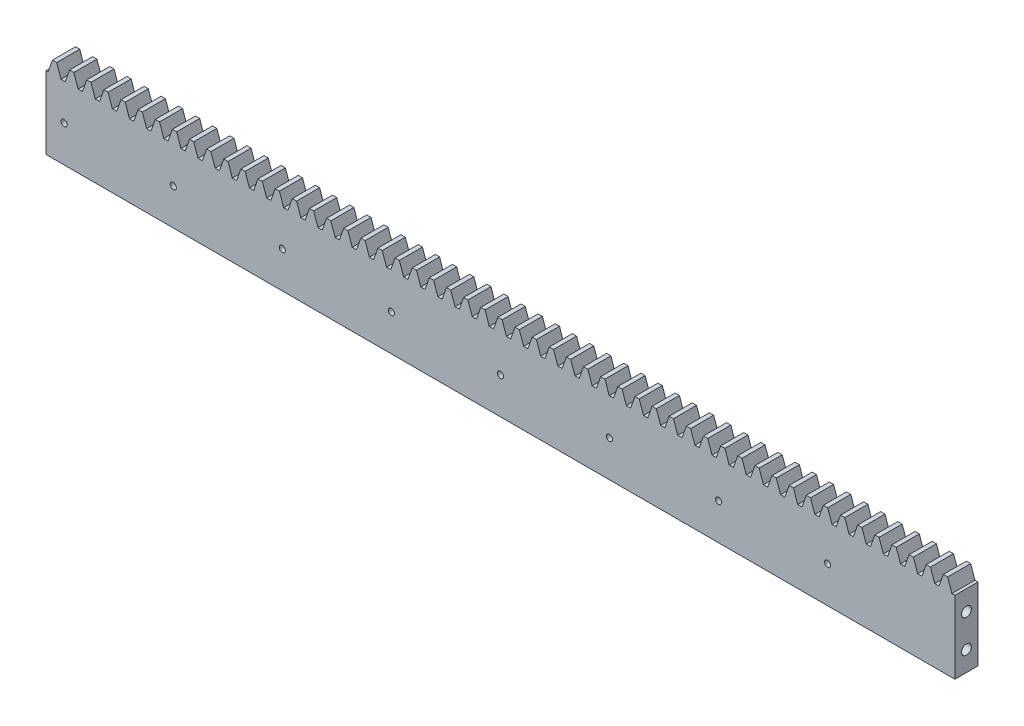
SolidWorks part; units mm, degrees
ref_plane "Front Plane" through (0, 0, 0) normal (0, 0, 1) x (1, 0, 0)
ref_plane "Top Plane" through (0, 0, 0) normal (0, 1, 0) x (1, 0, 0)
ref_plane "Right Plane" through (0, 0, 0) normal (1, 0, 0) x (0, 0, -1)
sketch "Original Sketch" plane through (0, 0, 0) normal (0, 0, 1) x (1, 0, 0)
  line L0 (5.3011, 16.625) -> (4.1236, 16.625) construction
  line L1 (4.1236, 16.625) -> (2.9446, 20) construction
  line L2 (2.9446, 20) -> (1.7677, 20) construction
  line L3 (1.7677, 20) -> (0.5887, 16.625) construction
  line L4 (0.5887, 16.625) -> (0, 16.625) construction
  line L5 (0, 16.625) -> (0, 0) construction
  line L6 (0, 0) -> (303, 0) construction
  line L7 (303, 0) -> (303, 18.9683) construction
  line L8 (303, 18.9683) -> (302.1814, 16.625) construction
  line L9 (302.1814, 16.625) -> (301.0039, 16.625) construction
  line L10 (301.0039, 16.625) -> (299.8249, 20) construction
  line L11 (299.8249, 20) -> (298.648, 20) construction
  line L12 (298.648, 20) -> (297.469, 16.625) construction
  line L13 (297.469, 16.625) -> (296.2915, 16.625) construction
  line L14 (296.2915, 16.625) -> (295.1125, 20) construction
  line L15 (295.1125, 20) -> (293.9356, 20) construction
  line L16 (293.9356, 20) -> (292.7566, 16.625) construction
  line L17 (292.7566, 16.625) -> (291.5791, 16.625) construction
  line L18 (291.5791, 16.625) -> (290.4001, 20) construction
  line L19 (290.4001, 20) -> (289.2232, 20) construction
  line L20 (289.2232, 20) -> (288.0442, 16.625) construction
  line L21 (288.0442, 16.625) -> (286.8667, 16.625) construction
  line L22 (286.8667, 16.625) -> (285.6877, 20) construction
  line L23 (285.6877, 20) -> (284.5109, 20) construction
  line L24 (284.5109, 20) -> (283.3318, 16.625) construction
  line L25 (283.3318, 16.625) -> (282.1544, 16.625) construction
  line L26 (282.1544, 16.625) -> (280.9753, 20) construction
  line L27 (280.9753, 20) -> (279.7985, 20) construction
  line L28 (279.7985, 20) -> (278.6195, 16.625) construction
  line L29 (278.6195, 16.625) -> (277.442, 16.625) construction
  line L30 (277.442, 16.625) -> (276.263, 20) construction
  line L31 (276.263, 20) -> (275.0861, 20) construction
  line L32 (275.0861, 20) -> (273.9071, 16.625) construction
  line L33 (273.9071, 16.625) -> (272.7296, 16.625) construction
  line L34 (272.7296, 16.625) -> (271.5506, 20) construction
  line L35 (271.5506, 20) -> (270.3737, 20) construction
  line L36 (270.3737, 20) -> (269.1947, 16.625) construction
  line L37 (269.1947, 16.625) -> (268.0172, 16.625) construction
  line L38 (268.0172, 16.625) -> (266.8382, 20) construction
  line L39 (266.8382, 20) -> (265.6613, 20) construction
  line L40 (265.6613, 20) -> (264.4823, 16.625) construction
  line L41 (264.4823, 16.625) -> (263.3048, 16.625) construction
  line L42 (263.3048, 16.625) -> (262.1258, 20) construction
  line L43 (262.1258, 20) -> (260.9489, 20) construction
  line L44 (260.9489, 20) -> (259.7699, 16.625) construction
  line L45 (259.7699, 16.625) -> (258.5924, 16.625) construction
  line L46 (258.5924, 16.625) -> (257.4134, 20) construction
  line L47 (257.4134, 20) -> (256.2365, 20) construction
  line L48 (256.2365, 20) -> (255.0575, 16.625) construction
  line L49 (255.0575, 16.625) -> (253.88, 16.625) construction
  line L50 (253.88, 16.625) -> (252.701, 20) construction
  line L51 (252.701, 20) -> (251.5242, 20) construction
  line L52 (251.5242, 20) -> (250.3452, 16.625) construction
  line L53 (250.3452, 16.625) -> (249.1677, 16.625) construction
  line L54 (249.1677, 16.625) -> (247.9887, 20) construction
  line L55 (247.9887, 20) -> (246.8118, 20) construction
  line L56 (246.8118, 20) -> (245.6328, 16.625) construction
  line L57 (245.6328, 16.625) -> (244.4553, 16.625) construction
  line L58 (244.4553, 16.625) -> (243.2763, 20) construction
  line L59 (243.2763, 20) -> (242.0994, 20) construction
  line L60 (242.0994, 20) -> (240.9204, 16.625) construction
  line L61 (240.9204, 16.625) -> (239.7429, 16.625) construction
  line L62 (239.7429, 16.625) -> (238.5639, 20) construction
  line L63 (238.5639, 20) -> (237.387, 20) construction
  line L64 (237.387, 20) -> (236.208, 16.625) construction
  line L65 (236.208, 16.625) -> (235.0305, 16.625) construction
  line L66 (235.0305, 16.625) -> (233.8515, 20) construction
  line L67 (233.8515, 20) -> (232.6746, 20) construction
  line L68 (232.6746, 20) -> (231.4956, 16.625) construction
  line L69 (231.4956, 16.625) -> (230.3181, 16.625) construction
  line L70 (230.3181, 16.625) -> (229.1391, 20) construction
  line L71 (229.1391, 20) -> (227.9622, 20) construction
  line L72 (227.9622, 20) -> (226.7832, 16.625) construction
  line L73 (226.7832, 16.625) -> (225.6057, 16.625) construction
  line L74 (225.6057, 16.625) -> (224.4267, 20) construction
  line L75 (224.4267, 20) -> (223.2498, 20) construction
  line L76 (223.2498, 20) -> (222.0708, 16.625) construction
  line L77 (222.0708, 16.625) -> (220.8933, 16.625) construction
  line L78 (220.8933, 16.625) -> (219.7143, 20) construction
  line L79 (219.7143, 20) -> (218.5375, 20) construction
  line L80 (218.5375, 20) -> (217.3585, 16.625) construction
  line L81 (217.3585, 16.625) -> (216.181, 16.625) construction
  line L82 (216.181, 16.625) -> (215.002, 20) construction
  line L83 (215.002, 20) -> (213.8251, 20) construction
  line L84 (213.8251, 20) -> (212.6461, 16.625) construction
  line L85 (212.6461, 16.625) -> (211.4686, 16.625) construction
  line L86 (211.4686, 16.625) -> (210.2896, 20) construction
  line L87 (210.2896, 20) -> (209.1127, 20) construction
  line L88 (209.1127, 20) -> (207.9337, 16.625) construction
  line L89 (207.9337, 16.625) -> (206.7562, 16.625) construction
  line L90 (206.7562, 16.625) -> (205.5772, 20) construction
  line L91 (205.5772, 20) -> (204.4003, 20) construction
  line L92 (204.4003, 20) -> (203.2213, 16.625) construction
  line L93 (203.2213, 16.625) -> (202.0438, 16.625) construction
  line L94 (202.0438, 16.625) -> (200.8648, 20) construction
  line L95 (200.8648, 20) -> (199.6879, 20) construction
  line L96 (199.6879, 20) -> (198.5089, 16.625) construction
  line L97 (198.5089, 16.625) -> (197.3314, 16.625) construction
  line L98 (197.3314, 16.625) -> (196.1524, 20) construction
  line L99 (196.1524, 20) -> (194.9755, 20) construction
  line L100 (194.9755, 20) -> (193.7965, 16.625) construction
  line L101 (193.7965, 16.625) -> (192.619, 16.625) construction
  line L102 (192.619, 16.625) -> (191.44, 20) construction
  line L103 (191.44, 20) -> (190.2631, 20) construction
  line L104 (190.2631, 20) -> (189.0841, 16.625) construction
  line L105 (189.0841, 16.625) -> (187.9067, 16.625) construction
  line L106 (187.9067, 16.625) -> (186.7276, 20) construction
  line L107 (186.7276, 20) -> (185.5508, 20) construction
  line L108 (185.5508, 20) -> (184.3718, 16.625) construction
  line L109 (184.3718, 16.625) -> (183.1943, 16.625) construction
  line L110 (183.1943, 16.625) -> (182.0153, 20) construction
  line L111 (182.0153, 20) -> (180.8384, 20) construction
  line L112 (180.8384, 20) -> (179.6594, 16.625) construction
  line L113 (179.6594, 16.625) -> (178.4819, 16.625) construction
  line L114 (178.4819, 16.625) -> (177.3029, 20) construction
  line L115 (177.3029, 20) -> (176.126, 20) construction
  line L116 (176.126, 20) -> (174.947, 16.625) construction
  line L117 (174.947, 16.625) -> (173.7695, 16.625) construction
  line L118 (173.7695, 16.625) -> (172.5905, 20) construction
  line L119 (172.5905, 20) -> (171.4136, 20) construction
  line L120 (171.4136, 20) -> (170.2346, 16.625) construction
  line L121 (170.2346, 16.625) -> (169.0571, 16.625) construction
  line L122 (169.0571, 16.625) -> (167.8781, 20) construction
  line L123 (167.8781, 20) -> (166.7012, 20) construction
  line L124 (166.7012, 20) -> (165.5222, 16.625) construction
  line L125 (165.5222, 16.625) -> (164.3447, 16.625) construction
  line L126 (164.3447, 16.625) -> (163.1657, 20) construction
  line L127 (163.1657, 20) -> (161.9888, 20) construction
  line L128 (161.9888, 20) -> (160.8098, 16.625) construction
  line L129 (160.8098, 16.625) -> (159.6323, 16.625) construction
  line L130 (159.6323, 16.625) -> (158.4533, 20) construction
  line L131 (158.4533, 20) -> (157.2765, 20) construction
  line L132 (157.2765, 20) -> (156.0975, 16.625) construction
  line L133 (156.0975, 16.625) -> (154.92, 16.625) construction
  line L134 (154.92, 16.625) -> (153.741, 20) construction
  line L135 (153.741, 20) -> (152.5641, 20) construction
  line L136 (152.5641, 20) -> (151.3851, 16.625) construction
  line L137 (151.3851, 16.625) -> (150.2076, 16.625) construction
  line L138 (150.2076, 16.625) -> (149.0286, 20) construction
  line L139 (149.0286, 20) -> (147.8517, 20) construction
  line L140 (147.8517, 20) -> (146.6727, 16.625) construction
  line L141 (146.6727, 16.625) -> (145.4952, 16.625) construction
  line L142 (145.4952, 16.625) -> (144.3162, 20) construction
  line L143 (144.3162, 20) -> (143.1393, 20) construction
  line L144 (143.1393, 20) -> (141.9603, 16.625) construction
  line L145 (141.9603, 16.625) -> (140.7828, 16.625) construction
  line L146 (140.7828, 16.625) -> (139.6038, 20) construction
  line L147 (139.6038, 20) -> (138.4269, 20) construction
  line L148 (138.4269, 20) -> (137.2479, 16.625) construction
  line L149 (137.2479, 16.625) -> (136.0704, 16.625) construction
  line L150 (136.0704, 16.625) -> (134.8914, 20) construction
  line L151 (134.8914, 20) -> (133.7145, 20) construction
  line L152 (133.7145, 20) -> (132.5355, 16.625) construction
  line L153 (132.5355, 16.625) -> (131.358, 16.625) construction
  line L154 (131.358, 16.625) -> (130.179, 20) construction
  line L155 (130.179, 20) -> (129.0021, 20) construction
  line L156 (129.0021, 20) -> (127.8231, 16.625) construction
  line L157 (127.8231, 16.625) -> (126.6456, 16.625) construction
  line L158 (126.6456, 16.625) -> (125.4666, 20) construction
  line L159 (125.4666, 20) -> (124.2898, 20) construction
  line L160 (124.2898, 20) -> (123.1108, 16.625) construction
  line L161 (123.1108, 16.625) -> (121.9333, 16.625) construction
  line L162 (121.9333, 16.625) -> (120.7543, 20) construction
  line L163 (120.7543, 20) -> (119.5774, 20) construction
  line L164 (119.5774, 20) -> (118.3984, 16.625) construction
  line L165 (118.3984, 16.625) -> (117.2209, 16.625) construction
  line L166 (117.2209, 16.625) -> (116.0419, 20) construction
  line L167 (116.0419, 20) -> (114.865, 20) construction
  line L168 (114.865, 20) -> (113.686, 16.625) construction
  line L169 (113.686, 16.625) -> (112.5085, 16.625) construction
  line L170 (112.5085, 16.625) -> (111.3295, 20) construction
  line L171 (111.3295, 20) -> (110.1526, 20) construction
  line L172 (110.1526, 20) -> (108.9736, 16.625) construction
  line L173 (108.9736, 16.625) -> (107.7961, 16.625) construction
  line L174 (107.7961, 16.625) -> (106.6171, 20) construction
  line L175 (106.6171, 20) -> (105.4402, 20) construction
  line L176 (105.4402, 20) -> (104.2612, 16.625) construction
  line L177 (104.2612, 16.625) -> (103.0837, 16.625) construction
  line L178 (103.0837, 16.625) -> (101.9047, 20) construction
  line L179 (101.9047, 20) -> (100.7278, 20) construction
  line L180 (100.7278, 20) -> (99.5488, 16.625) construction
  line L181 (99.5488, 16.625) -> (98.3713, 16.625) construction
  line L182 (98.3713, 16.625) -> (97.1923, 20) construction
  line L183 (97.1923, 20) -> (96.0155, 20) construction
  line L184 (96.0155, 20) -> (94.8364, 16.625) construction
  line L185 (94.8364, 16.625) -> (93.659, 16.625) construction
  line L186 (93.659, 16.625) -> (92.48, 20) construction
  line L187 (92.48, 20) -> (91.3031, 20) construction
  line L188 (91.3031, 20) -> (90.1241, 16.625) construction
  line L189 (90.1241, 16.625) -> (88.9466, 16.625) construction
  line L190 (88.9466, 16.625) -> (87.7676, 20) construction
  line L191 (87.7676, 20) -> (86.5907, 20) construction
  line L192 (86.5907, 20) -> (85.4117, 16.625) construction
  line L193 (85.4117, 16.625) -> (84.2342, 16.625) construction
  line L194 (84.2342, 16.625) -> (83.0552, 20) construction
  line L195 (83.0552, 20) -> (81.8783, 20) construction
  line L196 (81.8783, 20) -> (80.6993, 16.625) construction
  line L197 (80.6993, 16.625) -> (79.5218, 16.625) construction
  line L198 (79.5218, 16.625) -> (78.3428, 20) construction
  line L199 (78.3428, 20) -> (77.1659, 20) construction
  line L200 (77.1659, 20) -> (75.9869, 16.625) construction
  line L201 (75.9869, 16.625) -> (74.8094, 16.625) construction
  line L202 (74.8094, 16.625) -> (73.6304, 20) construction
  line L203 (73.6304, 20) -> (72.4535, 20) construction
  line L204 (72.4535, 20) -> (71.2745, 16.625) construction
  line L205 (71.2745, 16.625) -> (70.097, 16.625) construction
  line L206 (70.097, 16.625) -> (68.918, 20) construction
  line L207 (68.918, 20) -> (67.7411, 20) construction
  line L208 (67.7411, 20) -> (66.5621, 16.625) construction
  line L209 (66.5621, 16.625) -> (65.3846, 16.625) construction
  line L210 (65.3846, 16.625) -> (64.2056, 20) construction
  line L211 (64.2056, 20) -> (63.0288, 20) construction
  line L212 (63.0288, 20) -> (61.8498, 16.625) construction
  line L213 (61.8498, 16.625) -> (60.6723, 16.625) construction
  line L214 (60.6723, 16.625) -> (59.4933, 20) construction
  line L215 (59.4933, 20) -> (58.3164, 20) construction
  line L216 (58.3164, 20) -> (57.1374, 16.625) construction
  line L217 (57.1374, 16.625) -> (55.9599, 16.625) construction
  line L218 (55.9599, 16.625) -> (54.7809, 20) construction
  line L219 (54.7809, 20) -> (53.604, 20) construction
  line L220 (53.604, 20) -> (52.425, 16.625) construction
  line L221 (52.425, 16.625) -> (51.2475, 16.625) construction
  line L222 (51.2475, 16.625) -> (50.0685, 20) construction
  line L223 (50.0685, 20) -> (48.8916, 20) construction
  line L224 (48.8916, 20) -> (47.7126, 16.625) construction
  line L225 (47.7126, 16.625) -> (46.5351, 16.625) construction
  line L226 (46.5351, 16.625) -> (45.3561, 20) construction
  line L227 (45.3561, 20) -> (44.1792, 20) construction
  line L228 (44.1792, 20) -> (43.0002, 16.625) construction
  line L229 (43.0002, 16.625) -> (41.8227, 16.625) construction
  line L230 (41.8227, 16.625) -> (40.6437, 20) construction
  line L231 (40.6437, 20) -> (39.4668, 20) construction
  line L232 (39.4668, 20) -> (38.2878, 16.625) construction
  line L233 (38.2878, 16.625) -> (37.1103, 16.625) construction
  line L234 (37.1103, 16.625) -> (35.9313, 20) construction
  line L235 (35.9313, 20) -> (34.7544, 20) construction
  line L236 (34.7544, 20) -> (33.5754, 16.625) construction
  line L237 (33.5754, 16.625) -> (32.3979, 16.625) construction
  line L238 (32.3979, 16.625) -> (31.2189, 20) construction
  line L239 (31.2189, 20) -> (30.0421, 20) construction
  line L240 (30.0421, 20) -> (28.8631, 16.625) construction
  line L241 (28.8631, 16.625) -> (27.6856, 16.625) construction
  line L242 (27.6856, 16.625) -> (26.5066, 20) construction
  line L243 (26.5066, 20) -> (25.3297, 20) construction
  line L244 (25.3297, 20) -> (24.1507, 16.625) construction
  line L245 (24.1507, 16.625) -> (22.9732, 16.625) construction
  line L246 (22.9732, 16.625) -> (21.7942, 20) construction
  line L247 (21.7942, 20) -> (20.6173, 20) construction
  line L248 (20.6173, 20) -> (19.4383, 16.625) construction
  line L249 (19.4383, 16.625) -> (18.2608, 16.625) construction
  line L250 (18.2608, 16.625) -> (17.0818, 20) construction
  line L251 (17.0818, 20) -> (15.9049, 20) construction
  line L252 (15.9049, 20) -> (14.7259, 16.625) construction
  line L253 (14.7259, 16.625) -> (13.5484, 16.625) construction
  line L254 (13.5484, 16.625) -> (12.3694, 20) construction
  line L255 (12.3694, 20) -> (11.1925, 20) construction
  line L256 (11.1925, 20) -> (10.0135, 16.625) construction
  line L257 (10.0135, 16.625) -> (8.836, 16.625) construction
  line L258 (8.836, 16.625) -> (7.657, 20) construction
  line L259 (7.657, 20) -> (6.4801, 20) construction
  line L260 (6.4801, 20) -> (5.3011, 16.625) construction
sketch "Sketch6" plane through (0, 0, 0) normal (0, 0, 1) x (1, 0, 0)
  line L2 (303, 0) -> (303, 18.9683) construction
  line L3 (303, 18.9683) -> (302.1814, 16.625) construction
  line L4 (302.1814, 16.625) -> (301.0039, 16.625) construction
  line L5 (301.0039, 16.625) -> (299.8249, 20) construction
  line L6 (299.8249, 20) -> (298.648, 20) construction
  line L7 (298.648, 20) -> (297.469, 16.625) construction
  line L8 (297.469, 16.625) -> (296.2915, 16.625) construction
  line L9 (296.2915, 16.625) -> (295.1125, 20) construction
  line L10 (295.1125, 20) -> (293.9356, 20) construction
  line L11 (293.9356, 20) -> (292.7566, 16.625) construction
  line L12 (292.7566, 16.625) -> (291.5791, 16.625) construction
  line L13 (291.5791, 16.625) -> (290.4001, 20) construction
  line L14 (290.4001, 20) -> (289.2232, 20) construction
  line L15 (289.2232, 20) -> (288.0442, 16.625) construction
  line L16 (288.0442, 16.625) -> (286.8667, 16.625) construction
  line L17 (286.8667, 16.625) -> (285.6877, 20) construction
  line L18 (285.6877, 20) -> (284.5109, 20) construction
  line L19 (284.5109, 20) -> (283.3318, 16.625) construction
  line L20 (283.3318, 16.625) -> (282.1544, 16.625) construction
  line L21 (282.1544, 16.625) -> (280.9753, 20) construction
  line L22 (280.9753, 20) -> (279.7985, 20) construction
  line L23 (279.7985, 20) -> (278.6195, 16.625) construction
  line L24 (278.6195, 16.625) -> (277.442, 16.625) construction
  line L25 (277.442, 16.625) -> (276.263, 20) construction
  line L26 (276.263, 20) -> (275.0861, 20) construction
  line L27 (275.0861, 20) -> (273.9071, 16.625) construction
  line L28 (273.9071, 16.625) -> (272.7296, 16.625) construction
  line L29 (272.7296, 16.625) -> (271.5506, 20) construction
  line L30 (271.5506, 20) -> (270.3737, 20) construction
  line L31 (270.3737, 20) -> (269.1947, 16.625) construction
  line L32 (269.1947, 16.625) -> (268.0172, 16.625) construction
  line L33 (268.0172, 16.625) -> (266.8382, 20) construction
  line L34 (266.8382, 20) -> (265.6613, 20) construction
  line L35 (265.6613, 20) -> (264.4823, 16.625) construction
  line L36 (264.4823, 16.625) -> (263.3048, 16.625) construction
  line L37 (263.3048, 16.625) -> (262.1258, 20) construction
  line L38 (262.1258, 20) -> (260.9489, 20) construction
  line L39 (260.9489, 20) -> (259.7699, 16.625) construction
  line L40 (259.7699, 16.625) -> (258.5924, 16.625) construction
  line L41 (258.5924, 16.625) -> (257.4134, 20) construction
  line L42 (257.4134, 20) -> (256.2365, 20) construction
  line L43 (256.2365, 20) -> (255.0575, 16.625) construction
  line L44 (255.0575, 16.625) -> (253.88, 16.625) construction
  line L45 (253.88, 16.625) -> (252.701, 20) construction
  line L46 (252.701, 20) -> (251.5242, 20) construction
  line L47 (251.5242, 20) -> (250.3452, 16.625) construction
  line L48 (250.3452, 16.625) -> (249.1677, 16.625) construction
  line L49 (249.1677, 16.625) -> (247.9887, 20) construction
  line L50 (247.9887, 20) -> (246.8118, 20) construction
  line L51 (246.8118, 20) -> (245.6328, 16.625) construction
  line L52 (245.6328, 16.625) -> (244.4553, 16.625) construction
  line L53 (244.4553, 16.625) -> (243.2763, 20) construction
  line L54 (243.2763, 20) -> (242.0994, 20) construction
  line L55 (242.0994, 20) -> (240.9204, 16.625) construction
  line L56 (240.9204, 16.625) -> (239.7429, 16.625) construction
  line L57 (239.7429, 16.625) -> (238.5639, 20) construction
  line L58 (238.5639, 20) -> (237.387, 20) construction
  line L59 (237.387, 20) -> (236.208, 16.625) construction
  line L60 (236.208, 16.625) -> (235.0305, 16.625) construction
  line L61 (235.0305, 16.625) -> (233.8515, 20) construction
  line L62 (233.8515, 20) -> (232.6746, 20) construction
  line L63 (232.6746, 20) -> (231.4956, 16.625) construction
  line L64 (231.4956, 16.625) -> (230.3181, 16.625) construction
  line L65 (230.3181, 16.625) -> (229.1391, 20) construction
  line L66 (229.1391, 20) -> (227.9622, 20) construction
  line L67 (227.9622, 20) -> (226.7832, 16.625) construction
  line L68 (226.7832, 16.625) -> (225.6057, 16.625) construction
  line L69 (225.6057, 16.625) -> (224.4267, 20) construction
  line L70 (224.4267, 20) -> (223.2498, 20) construction
  line L71 (223.2498, 20) -> (222.0708, 16.625) construction
  line L72 (222.0708, 16.625) -> (220.8933, 16.625) construction
  line L73 (220.8933, 16.625) -> (219.7143, 20) construction
  line L74 (219.7143, 20) -> (218.5375, 20) construction
  line L75 (218.5375, 20) -> (217.3585, 16.625) construction
  line L76 (217.3585, 16.625) -> (216.181, 16.625) construction
  line L77 (216.181, 16.625) -> (215.002, 20) construction
  line L78 (215.002, 20) -> (213.8251, 20) construction
  line L79 (213.8251, 20) -> (212.6461, 16.625) construction
  line L80 (212.6461, 16.625) -> (211.4686, 16.625) construction
  line L81 (211.4686, 16.625) -> (210.2896, 20) construction
  line L82 (210.2896, 20) -> (209.1127, 20) construction
  line L83 (209.1127, 20) -> (207.9337, 16.625) construction
  line L84 (207.9337, 16.625) -> (206.7562, 16.625) construction
  line L85 (206.7562, 16.625) -> (205.5772, 20) construction
  line L86 (205.5772, 20) -> (204.4003, 20) construction
  line L87 (204.4003, 20) -> (203.2213, 16.625) construction
  line L88 (203.2213, 16.625) -> (202.0438, 16.625) construction
  line L89 (202.0438, 16.625) -> (200.8648, 20) construction
  line L90 (200.8648, 20) -> (199.6879, 20) construction
  line L91 (199.6879, 20) -> (198.5089, 16.625) construction
  line L92 (198.5089, 16.625) -> (197.3314, 16.625) construction
  line L93 (197.3314, 16.625) -> (196.1524, 20) construction
  line L94 (196.1524, 20) -> (194.9755, 20) construction
  line L95 (194.9755, 20) -> (193.7965, 16.625) construction
  line L96 (193.7965, 16.625) -> (192.619, 16.625) construction
  line L97 (192.619, 16.625) -> (191.44, 20) construction
  line L98 (191.44, 20) -> (190.2631, 20) construction
  line L99 (190.2631, 20) -> (189.0841, 16.625) construction
  line L100 (189.0841, 16.625) -> (187.9067, 16.625) construction
  line L101 (187.9067, 16.625) -> (186.7276, 20) construction
  line L102 (186.7276, 20) -> (185.5508, 20) construction
  line L103 (185.5508, 20) -> (184.3718, 16.625) construction
  line L104 (184.3718, 16.625) -> (183.1943, 16.625) construction
  line L105 (183.1943, 16.625) -> (182.0153, 20) construction
  line L106 (182.0153, 20) -> (180.8384, 20) construction
  line L107 (180.8384, 20) -> (179.6594, 16.625) construction
  line L108 (179.6594, 16.625) -> (178.4819, 16.625) construction
  line L109 (178.4819, 16.625) -> (177.3029, 20) construction
  line L110 (177.3029, 20) -> (176.126, 20) construction
  line L111 (176.126, 20) -> (174.947, 16.625) construction
  line L112 (174.947, 16.625) -> (173.7695, 16.625) construction
  line L113 (173.7695, 16.625) -> (172.5905, 20) construction
  line L114 (172.5905, 20) -> (171.4136, 20) construction
  line L115 (171.4136, 20) -> (170.2346, 16.625) construction
  line L116 (170.2346, 16.625) -> (169.0571, 16.625) construction
  line L117 (169.0571, 16.625) -> (167.8781, 20) construction
  line L118 (167.8781, 20) -> (166.7012, 20) construction
  line L119 (166.7012, 20) -> (165.5222, 16.625) construction
  line L120 (165.5222, 16.625) -> (164.3447, 16.625) construction
  line L121 (164.3447, 16.625) -> (163.1657, 20) construction
  line L122 (163.1657, 20) -> (161.9888, 20) construction
  line L123 (161.9888, 20) -> (160.8098, 16.625) construction
  line L124 (160.8098, 16.625) -> (159.6323, 16.625) construction
  line L125 (159.6323, 16.625) -> (158.4533, 20) construction
  line L126 (158.4533, 20) -> (157.2765, 20) construction
  line L127 (157.2765, 20) -> (156.0975, 16.625) construction
  line L128 (156.0975, 16.625) -> (154.92, 16.625) construction
  line L129 (154.92, 16.625) -> (153.741, 20) construction
  line L130 (153.741, 20) -> (152.5641, 20) construction
  line L131 (152.5641, 20) -> (151.3851, 16.625) construction
  line L132 (151.3851, 16.625) -> (150.2076, 16.625) construction
  line L133 (150.2076, 16.625) -> (149.0286, 20) construction
  line L134 (149.0286, 20) -> (147.8517, 20) construction
  line L135 (147.8517, 20) -> (146.6727, 16.625) construction
  line L136 (146.6727, 16.625) -> (145.4952, 16.625) construction
  line L137 (145.4952, 16.625) -> (144.3162, 20) construction
  line L138 (144.3162, 20) -> (143.1393, 20) construction
  line L139 (143.1393, 20) -> (141.9603, 16.625) construction
  line L140 (141.9603, 16.625) -> (140.7828, 16.625) construction
  line L141 (140.7828, 16.625) -> (139.6038, 20) construction
  line L142 (139.6038, 20) -> (138.4269, 20) construction
  line L143 (138.4269, 20) -> (137.2479, 16.625) construction
  line L144 (137.2479, 16.625) -> (136.0704, 16.625) construction
  line L145 (136.0704, 16.625) -> (134.8914, 20) construction
  line L146 (134.8914, 20) -> (133.7145, 20) construction
  line L147 (133.7145, 20) -> (132.5355, 16.625) construction
  line L148 (132.5355, 16.625) -> (131.358, 16.625) construction
  line L149 (131.358, 16.625) -> (130.179, 20) construction
  line L150 (130.179, 20) -> (129.0021, 20) construction
  line L151 (129.0021, 20) -> (127.8231, 16.625) construction
  line L152 (127.8231, 16.625) -> (126.6456, 16.625) construction
  line L153 (126.6456, 16.625) -> (125.4666, 20) construction
  line L154 (125.4666, 20) -> (124.2898, 20) construction
  line L155 (124.2898, 20) -> (123.1108, 16.625) construction
  line L156 (123.1108, 16.625) -> (121.9333, 16.625) construction
  line L157 (121.9333, 16.625) -> (120.7543, 20) construction
  line L158 (120.7543, 20) -> (119.5774, 20) construction
  line L159 (119.5774, 20) -> (118.3984, 16.625) construction
  line L160 (118.3984, 16.625) -> (117.2209, 16.625) construction
  line L161 (117.2209, 16.625) -> (116.0419, 20) construction
  line L162 (116.0419, 20) -> (114.865, 20) construction
  line L163 (114.865, 20) -> (113.686, 16.625) construction
  line L164 (113.686, 16.625) -> (112.5085, 16.625) construction
  line L165 (112.5085, 16.625) -> (111.3295, 20) construction
  line L166 (111.3295, 20) -> (110.1526, 20) construction
  line L167 (110.1526, 20) -> (108.9736, 16.625) construction
  line L168 (108.9736, 16.625) -> (107.7961, 16.625) construction
  line L169 (107.7961, 16.625) -> (106.6171, 20) construction
  line L170 (106.6171, 20) -> (105.4402, 20) construction
  line L171 (105.4402, 20) -> (104.2612, 16.625) construction
  line L172 (104.2612, 16.625) -> (103.0837, 16.625) construction
  line L173 (103.0837, 16.625) -> (101.9047, 20) construction
  line L174 (101.9047, 20) -> (100.7278, 20) construction
  line L175 (100.7278, 20) -> (99.5488, 16.625) construction
  line L176 (99.5488, 16.625) -> (98.3713, 16.625) construction
  line L177 (98.3713, 16.625) -> (97.1923, 20) construction
  line L178 (97.1923, 20) -> (96.0155, 20) construction
  line L179 (96.0155, 20) -> (94.8364, 16.625) construction
  line L180 (94.8364, 16.625) -> (93.659, 16.625) construction
  line L181 (93.659, 16.625) -> (92.48, 20) construction
  line L182 (92.48, 20) -> (91.3031, 20) construction
  line L183 (91.3031, 20) -> (90.1241, 16.625) construction
  line L184 (90.1241, 16.625) -> (88.9466, 16.625) construction
  line L185 (88.9466, 16.625) -> (87.7676, 20) construction
  line L186 (87.7676, 20) -> (86.5907, 20) construction
  line L187 (86.5907, 20) -> (85.4117, 16.625) construction
  line L188 (85.4117, 16.625) -> (84.2342, 16.625) construction
  line L189 (84.2342, 16.625) -> (83.0552, 20) construction
  line L190 (83.0552, 20) -> (81.8783, 20) construction
  line L191 (81.8783, 20) -> (80.6993, 16.625) construction
  line L192 (80.6993, 16.625) -> (79.5218, 16.625) construction
  line L193 (79.5218, 16.625) -> (78.3428, 20) construction
  line L194 (78.3428, 20) -> (77.1659, 20) construction
  line L195 (77.1659, 20) -> (75.9869, 16.625) construction
  line L196 (75.9869, 16.625) -> (74.8094, 16.625) construction
  line L197 (74.8094, 16.625) -> (73.6304, 20) construction
  line L198 (73.6304, 20) -> (72.4535, 20) construction
  line L199 (72.4535, 20) -> (71.2745, 16.625) construction
  line L200 (71.2745, 16.625) -> (70.097, 16.625) construction
  line L201 (70.097, 16.625) -> (68.918, 20) construction
  line L202 (68.918, 20) -> (67.7411, 20) construction
  line L203 (67.7411, 20) -> (66.5621, 16.625) construction
  line L204 (66.5621, 16.625) -> (65.3846, 16.625) construction
  line L205 (65.3846, 16.625) -> (64.2056, 20) construction
  line L206 (64.2056, 20) -> (63.0288, 20) construction
  line L207 (63.0288, 20) -> (61.8498, 16.625) construction
  line L208 (61.8498, 16.625) -> (60.6723, 16.625) construction
  line L209 (60.6723, 16.625) -> (59.4933, 20) construction
  line L210 (59.4933, 20) -> (58.3164, 20) construction
  line L211 (58.3164, 20) -> (57.1374, 16.625) construction
  line L212 (57.1374, 16.625) -> (55.9599, 16.625) construction
  line L213 (55.9599, 16.625) -> (54.7809, 20) construction
  line L214 (54.7809, 20) -> (53.604, 20) construction
  line L215 (53.604, 20) -> (52.425, 16.625) construction
  line L216 (52.425, 16.625) -> (51.2475, 16.625) construction
  line L217 (51.2475, 16.625) -> (50.0685, 20) construction
  line L218 (50.0685, 20) -> (48.8916, 20) construction
  line L219 (48.8916, 20) -> (47.7126, 16.625) construction
  line L220 (47.7126, 16.625) -> (46.5351, 16.625) construction
  line L221 (46.5351, 16.625) -> (45.3561, 20) construction
  line L222 (45.3561, 20) -> (44.1792, 20) construction
  line L223 (44.1792, 20) -> (43.0002, 16.625) construction
  line L224 (43.0002, 16.625) -> (41.8227, 16.625) construction
  line L225 (41.8227, 16.625) -> (40.6437, 20) construction
  line L226 (40.6437, 20) -> (39.4668, 20) construction
  line L227 (39.4668, 20) -> (38.2878, 16.625) construction
  line L228 (38.2878, 16.625) -> (37.1103, 16.625) construction
  line L229 (37.1103, 16.625) -> (35.9313, 20) construction
  line L230 (35.9313, 20) -> (34.7544, 20) construction
  line L231 (34.7544, 20) -> (33.5754, 16.625) construction
  line L232 (33.5754, 16.625) -> (32.3979, 16.625) construction
  line L233 (32.3979, 16.625) -> (31.2189, 20) construction
  line L234 (31.2189, 20) -> (30.0421, 20) construction
  line L235 (30.0421, 20) -> (28.8631, 16.625) construction
  line L236 (28.8631, 16.625) -> (27.6856, 16.625) construction
  line L237 (27.6856, 16.625) -> (26.5066, 20) construction
  line L238 (26.5066, 20) -> (25.3297, 20) construction
  line L239 (25.3297, 20) -> (24.1507, 16.625) construction
  line L240 (24.1507, 16.625) -> (22.9732, 16.625) construction
  line L241 (22.9732, 16.625) -> (21.7942, 20) construction
  line L242 (21.7942, 20) -> (20.6173, 20) construction
  line L243 (20.6173, 20) -> (19.4383, 16.625) construction
  line L244 (19.4383, 16.625) -> (18.2608, 16.625) construction
  line L245 (18.2608, 16.625) -> (17.0818, 20) construction
  line L246 (17.0818, 20) -> (15.9049, 20) construction
  line L247 (15.9049, 20) -> (14.7259, 16.625) construction
  line L248 (14.7259, 16.625) -> (13.5484, 16.625) construction
  line L249 (13.5484, 16.625) -> (12.3694, 20) construction
  line L250 (12.3694, 20) -> (11.1925, 20) construction
  line L251 (11.1925, 20) -> (10.0135, 16.625) construction
  line L252 (10.0135, 16.625) -> (8.836, 16.625) construction
  line L253 (8.836, 16.625) -> (7.657, 20) construction
  line L254 (7.657, 20) -> (6.4801, 20) construction
  line L255 (6.4801, 20) -> (5.3011, 16.625) construction
  line L256 (5.3011, 16.625) -> (4.1236, 16.625) construction
  line L257 (4.1236, 16.625) -> (2.9446, 20) construction
  line L258 (2.9446, 20) -> (1.7677, 20) construction
  line L259 (1.7677, 20) -> (0.5887, 16.625) construction
  line L260 (0.5887, 16.625) -> (0, 16.625) construction
  line L263 (303, 0) -> (303, 18.9683)
  line L264 (303, 18.9683) -> (302.1814, 16.625)
  line L265 (302.1814, 16.625) -> (301.0039, 16.625)
  line L266 (301.0039, 16.625) -> (299.8249, 20)
  line L267 (299.8249, 20) -> (298.648, 20)
  line L268 (298.648, 20) -> (297.469, 16.625)
  line L269 (297.469, 16.625) -> (296.2915, 16.625)
  line L270 (296.2915, 16.625) -> (295.1125, 20)
  line L271 (295.1125, 20) -> (293.9356, 20)
  line L272 (293.9356, 20) -> (292.7566, 16.625)
  line L273 (292.7566, 16.625) -> (291.5791, 16.625)
  line L274 (291.5791, 16.625) -> (290.4001, 20)
  line L275 (290.4001, 20) -> (289.2232, 20)
  line L276 (289.2232, 20) -> (288.0442, 16.625)
  line L277 (288.0442, 16.625) -> (286.8667, 16.625)
  line L278 (286.8667, 16.625) -> (285.6877, 20)
  line L279 (285.6877, 20) -> (284.5109, 20)
  line L280 (284.5109, 20) -> (283.3318, 16.625)
  line L281 (283.3318, 16.625) -> (282.1544, 16.625)
  line L282 (282.1544, 16.625) -> (280.9753, 20)
  line L283 (280.9753, 20) -> (279.7985, 20)
  line L284 (279.7985, 20) -> (278.6195, 16.625)
  line L285 (278.6195, 16.625) -> (277.442, 16.625)
  line L286 (277.442, 16.625) -> (276.263, 20)
  line L287 (276.263, 20) -> (275.0861, 20)
  line L288 (275.0861, 20) -> (273.9071, 16.625)
  line L289 (273.9071, 16.625) -> (272.7296, 16.625)
  line L290 (272.7296, 16.625) -> (271.5506, 20)
  line L291 (271.5506, 20) -> (270.3737, 20)
  line L292 (270.3737, 20) -> (269.1947, 16.625)
  line L293 (269.1947, 16.625) -> (268.0172, 16.625)
  line L294 (268.0172, 16.625) -> (266.8382, 20)
  line L295 (266.8382, 20) -> (265.6613, 20)
  line L296 (265.6613, 20) -> (264.4823, 16.625)
  line L297 (264.4823, 16.625) -> (263.3048, 16.625)
  line L298 (263.3048, 16.625) -> (262.1258, 20)
  line L299 (262.1258, 20) -> (260.9489, 20)
  line L300 (260.9489, 20) -> (259.7699, 16.625)
  line L301 (259.7699, 16.625) -> (258.5924, 16.625)
  line L302 (258.5924, 16.625) -> (257.4134, 20)
  line L303 (257.4134, 20) -> (256.2365, 20)
  line L304 (256.2365, 20) -> (255.0575, 16.625)
  line L305 (255.0575, 16.625) -> (253.88, 16.625)
  line L306 (253.88, 16.625) -> (252.701, 20)
  line L307 (252.701, 20) -> (251.5242, 20)
  line L308 (251.5242, 20) -> (250.3452, 16.625)
  line L309 (250.3452, 16.625) -> (249.1677, 16.625)
  line L310 (249.1677, 16.625) -> (247.9887, 20)
  line L311 (247.9887, 20) -> (246.8118, 20)
  line L312 (246.8118, 20) -> (245.6328, 16.625)
  line L313 (245.6328, 16.625) -> (244.4553, 16.625)
  line L314 (244.4553, 16.625) -> (243.2763, 20)
  line L315 (243.2763, 20) -> (242.0994, 20)
  line L316 (242.0994, 20) -> (240.9204, 16.625)
  line L317 (240.9204, 16.625) -> (239.7429, 16.625)
  line L318 (239.7429, 16.625) -> (238.5639, 20)
  line L319 (238.5639, 20) -> (237.387, 20)
  line L320 (237.387, 20) -> (236.208, 16.625)
  line L321 (236.208, 16.625) -> (235.0305, 16.625)
  line L322 (235.0305, 16.625) -> (233.8515, 20)
  line L323 (233.8515, 20) -> (232.6746, 20)
  line L324 (232.6746, 20) -> (231.4956, 16.625)
  line L325 (231.4956, 16.625) -> (230.3181, 16.625)
  line L326 (230.3181, 16.625) -> (229.1391, 20)
  line L327 (229.1391, 20) -> (227.9622, 20)
  line L328 (227.9622, 20) -> (226.7832, 16.625)
  line L329 (226.7832, 16.625) -> (225.6057, 16.625)
  line L330 (225.6057, 16.625) -> (224.4267, 20)
  line L331 (224.4267, 20) -> (223.2498, 20)
  line L332 (223.2498, 20) -> (222.0708, 16.625)
  line L333 (222.0708, 16.625) -> (220.8933, 16.625)
  line L334 (220.8933, 16.625) -> (219.7143, 20)
  line L335 (219.7143, 20) -> (218.5375, 20)
  line L336 (218.5375, 20) -> (217.3585, 16.625)
  line L337 (217.3585, 16.625) -> (216.181, 16.625)
  line L338 (216.181, 16.625) -> (215.002, 20)
  line L339 (215.002, 20) -> (213.8251, 20)
  line L340 (213.8251, 20) -> (212.6461, 16.625)
  line L341 (212.6461, 16.625) -> (211.4686, 16.625)
  line L342 (211.4686, 16.625) -> (210.2896, 20)
  line L343 (210.2896, 20) -> (209.1127, 20)
  line L344 (209.1127, 20) -> (207.9337, 16.625)
  line L345 (207.9337, 16.625) -> (206.7562, 16.625)
  line L346 (206.7562, 16.625) -> (205.5772, 20)
  line L347 (205.5772, 20) -> (204.4003, 20)
  line L348 (204.4003, 20) -> (203.2213, 16.625)
  line L349 (203.2213, 16.625) -> (202.0438, 16.625)
  line L350 (202.0438, 16.625) -> (200.8648, 20)
  line L351 (200.8648, 20) -> (199.6879, 20)
  line L352 (199.6879, 20) -> (198.5089, 16.625)
  line L353 (198.5089, 16.625) -> (197.3314, 16.625)
  line L354 (197.3314, 16.625) -> (196.1524, 20)
  line L355 (196.1524, 20) -> (194.9755, 20)
  line L356 (194.9755, 20) -> (193.7965, 16.625)
  line L357 (193.7965, 16.625) -> (192.619, 16.625)
  line L358 (192.619, 16.625) -> (191.44, 20)
  line L359 (191.44, 20) -> (190.2631, 20)
  line L360 (190.2631, 20) -> (189.0841, 16.625)
  line L361 (189.0841, 16.625) -> (187.9067, 16.625)
  line L362 (187.9067, 16.625) -> (186.7276, 20)
  line L363 (186.7276, 20) -> (185.5508, 20)
  line L364 (185.5508, 20) -> (184.3718, 16.625)
  line L365 (184.3718, 16.625) -> (183.1943, 16.625)
  line L366 (183.1943, 16.625) -> (182.0153, 20)
  line L367 (182.0153, 20) -> (180.8384, 20)
  line L368 (180.8384, 20) -> (179.6594, 16.625)
  line L369 (179.6594, 16.625) -> (178.4819, 16.625)
  line L370 (178.4819, 16.625) -> (177.3029, 20)
  line L371 (177.3029, 20) -> (176.126, 20)
  line L372 (176.126, 20) -> (174.947, 16.625)
  line L373 (174.947, 16.625) -> (173.7695, 16.625)
  line L374 (173.7695, 16.625) -> (172.5905, 20)
  line L375 (172.5905, 20) -> (171.4136, 20)
  line L376 (171.4136, 20) -> (170.2346, 16.625)
  line L377 (170.2346, 16.625) -> (169.0571, 16.625)
  line L378 (169.0571, 16.625) -> (167.8781, 20)
  line L379 (167.8781, 20) -> (166.7012, 20)
  line L380 (166.7012, 20) -> (165.5222, 16.625)
  line L381 (165.5222, 16.625) -> (164.3447, 16.625)
  line L382 (164.3447, 16.625) -> (163.1657, 20)
  line L383 (163.1657, 20) -> (161.9888, 20)
  line L384 (161.9888, 20) -> (160.8098, 16.625)
  line L385 (160.8098, 16.625) -> (159.6323, 16.625)
  line L386 (159.6323, 16.625) -> (158.4533, 20)
  line L387 (158.4533, 20) -> (157.2765, 20)
  line L388 (157.2765, 20) -> (156.0975, 16.625)
  line L389 (156.0975, 16.625) -> (154.92, 16.625)
  line L390 (154.92, 16.625) -> (153.741, 20)
  line L391 (153.741, 20) -> (152.5641, 20)
  line L392 (152.5641, 20) -> (151.3851, 16.625)
  line L393 (151.3851, 16.625) -> (150.2076, 16.625)
  line L394 (150.2076, 16.625) -> (149.0286, 20)
  line L395 (149.0286, 20) -> (147.8517, 20)
  line L396 (147.8517, 20) -> (146.6727, 16.625)
  line L397 (146.6727, 16.625) -> (145.4952, 16.625)
  line L398 (145.4952, 16.625) -> (144.3162, 20)
  line L399 (144.3162, 20) -> (143.1393, 20)
  line L400 (143.1393, 20) -> (141.9603, 16.625)
  line L401 (141.9603, 16.625) -> (140.7828, 16.625)
  line L402 (140.7828, 16.625) -> (139.6038, 20)
  line L403 (139.6038, 20) -> (138.4269, 20)
  line L404 (138.4269, 20) -> (137.2479, 16.625)
  line L405 (137.2479, 16.625) -> (136.0704, 16.625)
  line L406 (136.0704, 16.625) -> (134.8914, 20)
  line L407 (134.8914, 20) -> (133.7145, 20)
  line L408 (133.7145, 20) -> (132.5355, 16.625)
  line L409 (132.5355, 16.625) -> (131.358, 16.625)
  line L410 (131.358, 16.625) -> (130.179, 20)
  line L411 (130.179, 20) -> (129.0021, 20)
  line L412 (129.0021, 20) -> (127.8231, 16.625)
  line L413 (127.8231, 16.625) -> (126.6456, 16.625)
  line L414 (126.6456, 16.625) -> (125.4666, 20)
  line L415 (125.4666, 20) -> (124.2898, 20)
  line L416 (124.2898, 20) -> (123.1108, 16.625)
  line L417 (123.1108, 16.625) -> (121.9333, 16.625)
  line L418 (121.9333, 16.625) -> (120.7543, 20)
  line L419 (120.7543, 20) -> (119.5774, 20)
  line L420 (119.5774, 20) -> (118.3984, 16.625)
  line L421 (118.3984, 16.625) -> (117.2209, 16.625)
  line L422 (117.2209, 16.625) -> (116.0419, 20)
  line L423 (116.0419, 20) -> (114.865, 20)
  line L424 (114.865, 20) -> (113.686, 16.625)
  line L425 (113.686, 16.625) -> (112.5085, 16.625)
  line L426 (112.5085, 16.625) -> (111.3295, 20)
  line L427 (111.3295, 20) -> (110.1526, 20)
  line L428 (110.1526, 20) -> (108.9736, 16.625)
  line L429 (108.9736, 16.625) -> (107.7961, 16.625)
  line L430 (107.7961, 16.625) -> (106.6171, 20)
  line L431 (106.6171, 20) -> (105.4402, 20)
  line L432 (105.4402, 20) -> (104.2612, 16.625)
  line L433 (104.2612, 16.625) -> (103.0837, 16.625)
  line L434 (103.0837, 16.625) -> (101.9047, 20)
  line L435 (101.9047, 20) -> (100.7278, 20)
  line L436 (100.7278, 20) -> (99.5488, 16.625)
  line L437 (99.5488, 16.625) -> (98.3713, 16.625)
  line L438 (98.3713, 16.625) -> (97.1923, 20)
  line L439 (97.1923, 20) -> (96.0155, 20)
  line L440 (96.0155, 20) -> (94.8364, 16.625)
  line L441 (94.8364, 16.625) -> (93.659, 16.625)
  line L442 (93.659, 16.625) -> (92.48, 20)
  line L443 (92.48, 20) -> (91.3031, 20)
  line L444 (91.3031, 20) -> (90.1241, 16.625)
  line L445 (90.1241, 16.625) -> (88.9466, 16.625)
  line L446 (88.9466, 16.625) -> (87.7676, 20)
  line L447 (87.7676, 20) -> (86.5907, 20)
  line L448 (86.5907, 20) -> (85.4117, 16.625)
  line L449 (85.4117, 16.625) -> (84.2342, 16.625)
  line L450 (84.2342, 16.625) -> (83.0552, 20)
  line L451 (83.0552, 20) -> (81.8783, 20)
  line L452 (81.8783, 20) -> (80.6993, 16.625)
  line L453 (80.6993, 16.625) -> (79.5218, 16.625)
  line L454 (79.5218, 16.625) -> (78.3428, 20)
  line L455 (78.3428, 20) -> (77.1659, 20)
  line L456 (77.1659, 20) -> (75.9869, 16.625)
  line L457 (75.9869, 16.625) -> (74.8094, 16.625)
  line L458 (74.8094, 16.625) -> (73.6304, 20)
  line L459 (73.6304, 20) -> (72.4535, 20)
  line L460 (72.4535, 20) -> (71.2745, 16.625)
  line L461 (71.2745, 16.625) -> (70.097, 16.625)
  line L462 (70.097, 16.625) -> (68.918, 20)
  line L463 (68.918, 20) -> (67.7411, 20)
  line L464 (67.7411, 20) -> (66.5621, 16.625)
  line L465 (66.5621, 16.625) -> (65.3846, 16.625)
  line L466 (65.3846, 16.625) -> (64.2056, 20)
  line L467 (64.2056, 20) -> (63.0288, 20)
  line L468 (63.0288, 20) -> (61.8498, 16.625)
  line L469 (61.8498, 16.625) -> (60.6723, 16.625)
  line L470 (60.6723, 16.625) -> (59.4933, 20)
  line L471 (59.4933, 20) -> (58.3164, 20)
  line L472 (58.3164, 20) -> (57.1374, 16.625)
  line L473 (57.1374, 16.625) -> (55.9599, 16.625)
  line L474 (55.9599, 16.625) -> (54.7809, 20)
  line L475 (54.7809, 20) -> (53.604, 20)
  line L476 (53.604, 20) -> (52.425, 16.625)
  line L477 (52.425, 16.625) -> (51.2475, 16.625)
  line L478 (51.2475, 16.625) -> (50.0685, 20)
  line L479 (50.0685, 20) -> (48.8916, 20)
  line L480 (48.8916, 20) -> (47.7126, 16.625)
  line L481 (47.7126, 16.625) -> (46.5351, 16.625)
  line L482 (46.5351, 16.625) -> (45.3561, 20)
  line L483 (45.3561, 20) -> (44.1792, 20)
  line L484 (44.1792, 20) -> (43.0002, 16.625)
  line L485 (43.0002, 16.625) -> (41.8227, 16.625)
  line L486 (41.8227, 16.625) -> (40.6437, 20)
  line L487 (40.6437, 20) -> (39.4668, 20)
  line L488 (39.4668, 20) -> (38.2878, 16.625)
  line L489 (38.2878, 16.625) -> (37.1103, 16.625)
  line L490 (37.1103, 16.625) -> (35.9313, 20)
  line L491 (35.9313, 20) -> (34.7544, 20)
  line L492 (34.7544, 20) -> (33.5754, 16.625)
  line L493 (33.5754, 16.625) -> (32.3979, 16.625)
  line L494 (32.3979, 16.625) -> (31.2189, 20)
  line L495 (31.2189, 20) -> (30.0421, 20)
  line L496 (30.0421, 20) -> (28.8631, 16.625)
  line L497 (28.8631, 16.625) -> (27.6856, 16.625)
  line L498 (27.6856, 16.625) -> (26.5066, 20)
  line L499 (26.5066, 20) -> (25.3297, 20)
  line L500 (25.3297, 20) -> (24.1507, 16.625)
  line L501 (24.1507, 16.625) -> (22.9732, 16.625)
  line L502 (22.9732, 16.625) -> (21.7942, 20)
  line L503 (21.7942, 20) -> (20.6173, 20)
  line L504 (20.6173, 20) -> (19.4383, 16.625)
  line L505 (19.4383, 16.625) -> (18.2608, 16.625)
  line L506 (18.2608, 16.625) -> (17.0818, 20)
  line L507 (17.0818, 20) -> (15.9049, 20)
  line L508 (15.9049, 20) -> (14.7259, 16.625)
  line L509 (14.7259, 16.625) -> (13.5484, 16.625)
  line L510 (13.5484, 16.625) -> (12.3694, 20)
  line L511 (12.3694, 20) -> (11.1925, 20)
  line L512 (11.1925, 20) -> (10.0135, 16.625)
  line L513 (10.0135, 16.625) -> (8.836, 16.625)
  line L514 (8.836, 16.625) -> (7.657, 20)
  line L515 (7.657, 20) -> (6.4801, 20)
  line L516 (6.4801, 20) -> (5.3011, 16.625)
  line L517 (5.3011, 16.625) -> (4.1236, 16.625)
  line L518 (4.1236, 16.625) -> (2.9446, 20)
  line L519 (2.9446, 20) -> (1.7677, 20)
  line L520 (1.7677, 20) -> (0.5887, 16.625)
  line L521 (0.5887, 16.625) -> (0, 16.625)
  line L522 (250, 16.625) -> (250, -3.375)
  line L523 (0, 16.625) -> (0, -3.375)
  line L524 (0, -3.375) -> (250, -3.375)
  circle A0 centre (215, 6.625) radius 0.85
  circle A3 centre (185, 6.625) radius 0.85
  circle A4 centre (155, 6.625) radius 0.85
  circle A5 centre (125, 6.625) radius 0.85
  circle A6 centre (95, 6.625) radius 0.85
  circle A7 centre (65, 6.625) radius 0.85
  circle A8 centre (35, 6.625) radius 0.85
  circle A9 centre (5, 6.625) radius 0.85
  dimension "D3" = 1.7
  dimension "D4" = 8
  dimension "D1" = 250
  dimension "D2" = 20
extrude "Boss-Extrude2" add sketch "Sketch6" along normal blind 6.35 contours L522 L309 L310 L311 L312 L313 L314 L315 L316 L317 L318 L319 L320 L321 L322 L323 L324 L325 L326 L327 L328 L329 L330 L331 L332 L333 L334 L335 L336 L337 L338 L339 L340 L341 L342 L343 L344 L345 L346 L347 L348 L349 L350 L351 L352 L353 L354 L355 L356 L357 L358 region at (125.0409, 7.5146, 0)
sketch "Sketch9" plane through (250, 0, 0) normal (1, 0, 0) x (0, 0, -1)
  circle A0 centre (-3.175, 2.125) radius 1.35
  circle A1 centre (-3.175, 11.125) radius 1.35
  dimension "D1" = 2.7
  dimension "D2" = 2.7
extrude "Cut-Extrude2" cut sketch "Sketch9" against normal blind 20
